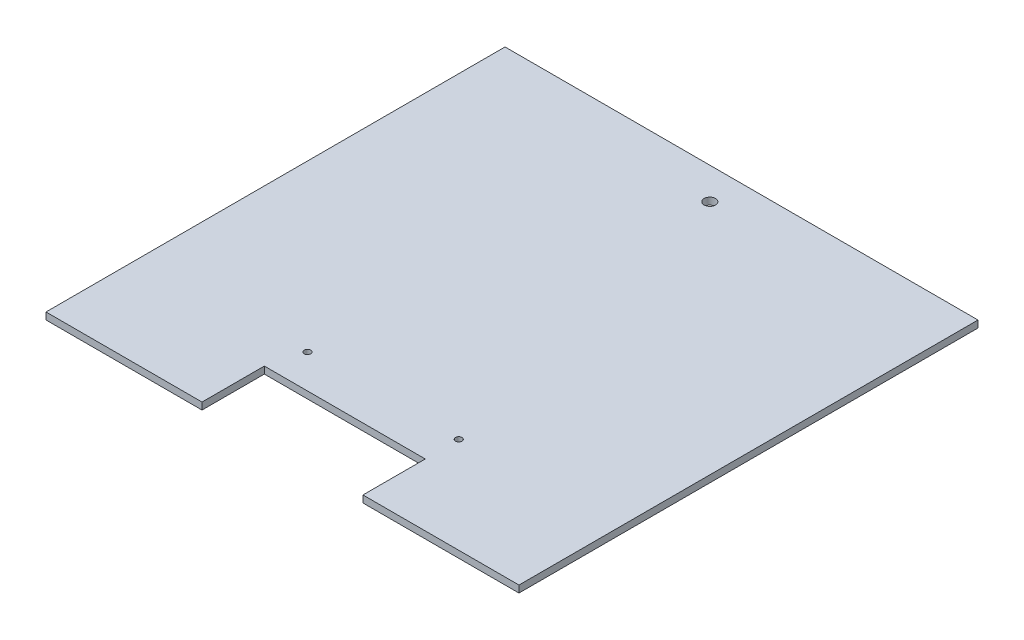
SolidWorks part; units mm, degrees
ref_plane "Front Plane" through (0, 0, 0) normal (0, 0, 1) x (1, 0, 0)
ref_plane "Top Plane" through (0, 0, 0) normal (0, 1, 0) x (1, 0, 0)
ref_plane "Right Plane" through (0, 0, 0) normal (1, 0, 0) x (0, 0, -1)
sketch "Sketch1" plane through (0, 0, 0) normal (0, 1, 0) x (1, 0, 0)
  line L1 (-94.869, -92.075) -> (94.869, -92.075)
  line L2 (-94.869, -92.075) -> (-94.869, 92.075)
  line L3 (-94.869, 92.075) -> (94.869, 92.075)
  line L4 (94.869, -92.075) -> (94.869, 92.075)
  line L5 (-94.869, -92.075) -> (94.869, 92.075) construction
  line L6 (-94.869, 92.075) -> (94.869, -92.075) construction
  point P0 (0, 0)
  dimension "D1" = 189.738
  dimension "D2" = 184.15
extrude "Boss-Extrude1" add sketch "Sketch1" along normal blind 2.794
sketch "Sketch2" plane through (0, 2.794, 0) normal (0, 1, 0) x (1, 0, 0)
  line L2 (94.869, 92.075) -> (-94.869, 92.075) construction
  circle A0 centre (0, 79.375) radius 2.286
  point P2 (0, 0)
  point P5 (0, 92.075)
  dimension "D1" = 4.572
  dimension "D2" = 12.7
extrude "Cut-Extrude1" cut sketch "Sketch2" against normal through all
sketch "Sketch3" plane through (0, 2.794, 0) normal (0, 1, 0) x (1, 0, 0)
  line L0 (0, -92.075) -> (-32.28, -92.075)
  line L1 (-94.869, -92.075) -> (94.869, -92.075) construction
  line L2 (-32.28, -92.075) -> (-32.28, -67.075)
  line L3 (-32.28, -67.075) -> (32.28, -67.075)
  line L4 (32.28, -67.075) -> (32.28, -92.075)
  line L5 (32.28, -92.075) -> (0, -92.075)
  point P5 (0, -67.075)
  dimension "D1" = 64.56
  dimension "D3" = 25
extrude "Cut-Extrude2" cut sketch "Sketch3" against normal through all
sketch "Sketch4" plane through (0, 2.794, 0) normal (0, 1, 0) x (1, 0, 0)
  line L5 (32.28, -67.075) -> (-32.28, -67.075) construction
  line L6 (-94.869, 92.075) -> (-94.869, -92.075) construction
  line L16 (36.98, 41.855) -> (36.98, -60.725)
  line L17 (36.98, 41.855) -> (-33.02, 41.855)
  line L18 (-33.02, 41.855) -> (-33.02, -60.725)
  line L19 (36.98, -60.725) -> (-33.02, -60.725)
  line L20 (36.98, 41.855) -> (-33.02, -60.725) construction
  line L21 (-33.02, 41.855) -> (36.98, -60.725) construction
  circle A6 centre (-28.54, -53.525) radius 1.3
  circle A7 centre (32.166, -53.525) radius 1.3
  point P28 (1.98, -9.435)
  dimension "D23" = 2.6
  dimension "D24" = 7.2
  dimension "D25" = 4.48
  dimension "D4" = 60.706
  dimension "D3" = 61.849
  dimension "D1" = 6.35
  dimension "D20" = 102.58
  dimension "D21" = 70
extrude "Cut-Extrude4" cut sketch "Sketch4" against normal through all contours A6 | A7
